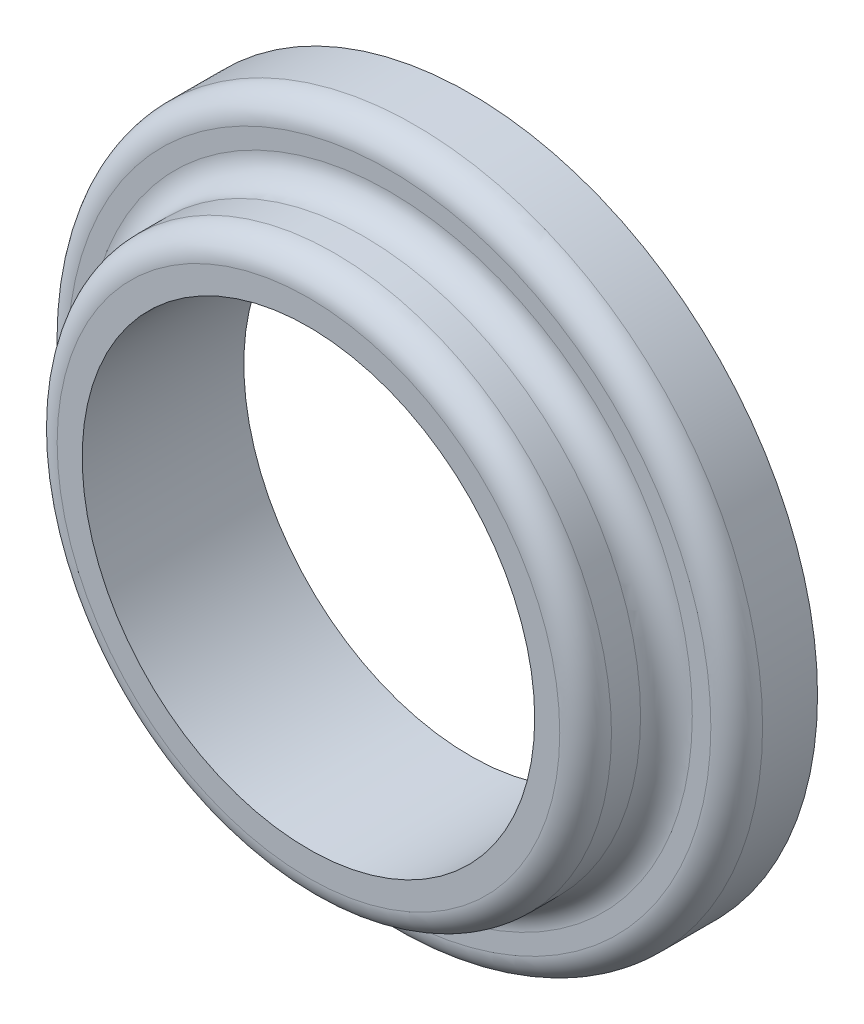
SolidWorks part; units mm, degrees
material "Nylon 101"
ref_plane "Front Plane" through (0, 0, 0) normal (0, 0, 1) x (1, 0, 0)
ref_plane "Top Plane" through (0, 0, 0) normal (0, 1, 0) x (1, 0, 0)
ref_plane "Right Plane" through (0, 0, 0) normal (1, 0, 0) x (0, 0, -1)
sketch "Sketch1" plane through (0, 0, 0) normal (0, 0, 1) x (1, 0, 0)
  circle A3 centre (-6.731, -165.7192) radius 6.8263
  circle A4 centre (-6.731, -165.7192) radius 4.445
  dimension "D1" = 2.3812
extrude "Boss-Extrude1" add sketch "Sketch1" along normal blind 1.5875
sketch "Sketch2" plane through (0, 0, 1.5875) normal (0, 0, 1) x (1, 0, 0)
  circle A0 centre (-6.731, -165.7192) radius 4.445 construction
  circle A1 centre (-6.731, -165.7192) radius 4.445
extrude "Extrude-Thin1" add sketch "Sketch2" along normal blind 1.5875 thin thin type one direction wall 1
fillet "Fillet1" radius 0.508 3 edges at (0.0953, -165.7192, 1.5875) (-1.286, -165.7192, 1.5875) (-1.286, -165.7192, 3.175)
